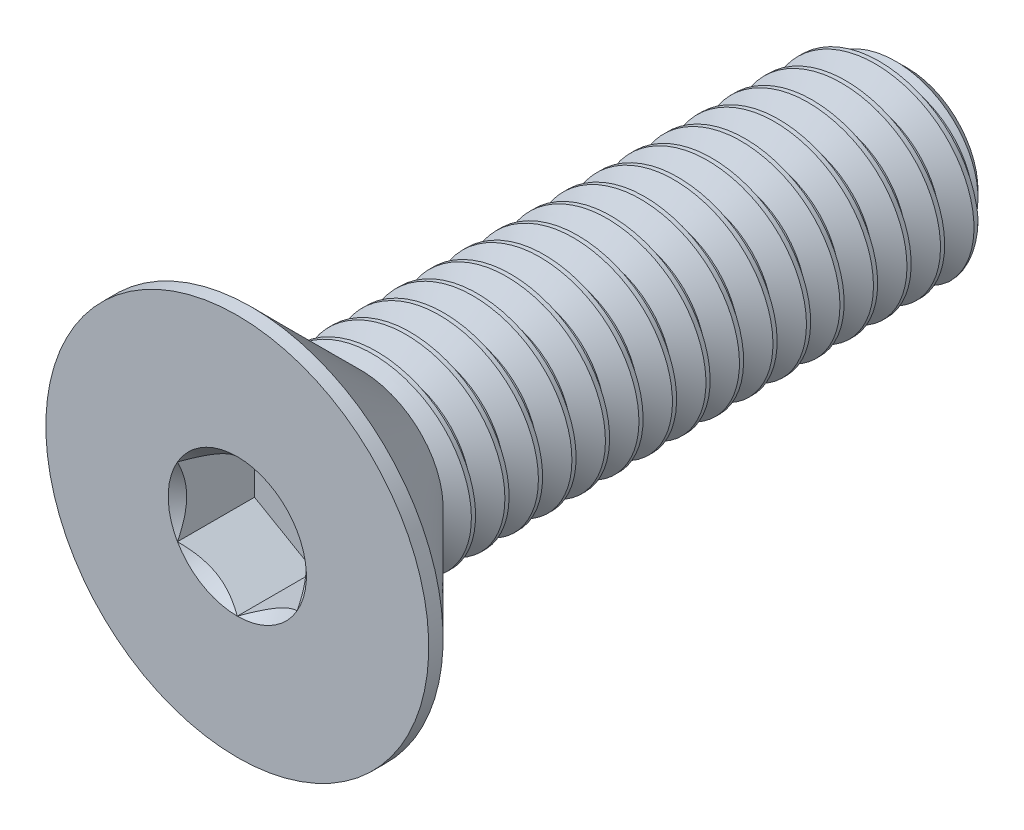
SolidWorks part; units mm, degrees
ref_plane "Front" through (0, 0, 0) normal (0, 0, 1) x (1, 0, 0)
ref_plane "Top" through (0, 0, 0) normal (0, 1, 0) x (1, 0, 0)
ref_plane "Right" through (0, 0, 0) normal (1, 0, 0) x (0, 0, -1)
sketch "Body Sketch" plane through (0, 0, 0) normal (1, 0, 0) x (0, 0, -1)
  line L0 (0, 4) -> (0.3, 4) construction
  line L1 (0.3, 4) -> (2.3, 2) construction
  line L2 (0, 2) -> (14, 2)
  line L3 (14, 2) -> (14, 0)
  line L4 (14, 0) -> (0, 0)
  line L5 (0, 0) -> (0, 4) construction
  line L6 (0, 4) -> (0, -4) construction
  line L7 (14, 2) -> (14, -2) construction
  line L8 (0, -4) -> (0.3, -4) construction
  line L9 (0.3, -4) -> (2.3, -2) construction
  line L11 (0, 2) -> (0, 0)
  line L12 (2.3, 2) -> (2.3, 0) construction
revolve "Body Revolve" add sketch "Body Sketch" angle 360 mid plane about L4
sketch "Sketch3" plane through (0, 0, -14) normal (0, 0, -1) x (-1, 0, 0)
  circle A0 centre (0, 0) radius 2
curve "Helix/Spiral1" pitch 0.7 height 14 radius 2 centre (0, 0, -14) axis (0, 0, 1) start towards (0, 1, 0)
sketch "Sketch2" plane through (0, 0, 0) normal (1, 0, 0) x (0, 0, -1)
  line L0 (14, 2) -> (14.6125, 2)
  line L1 (14.6125, 2) -> (14.35, 1.5453)
  line L2 (14.35, 1.5453) -> (14.2625, 1.5453)
  line L3 (14.2625, 1.5453) -> (14, 2)
  line L4 (14.1312, 1.7727) -> (14.4813, 1.7727) construction
  dimension "D1" = 60
  dimension "D2" = 0.0875
  dimension "D3" = 0.35
chamfer "Chamfer1" distance 0.525 angle 45 1 edges at (0, 2, -14)
sweep "Cut-Sweep1" cut profiles "Sketch2" path "Helix/Spiral1" align with end faces yes
sketch "Head Sketch" plane through (0, 0, 0) normal (1, 0, 0) x (0, 0, -1)
  line L0 (0, 4) -> (0.3, 4) construction
  line L1 (0.3, 4) -> (2.3, 2) construction
  line L2 (0, 4) -> (0.3, 4)
  line L3 (0.3, 4) -> (2.3, 2)
  line L4 (2.3, 2) -> (2.3, 0) construction
  line L5 (2.3, 2) -> (2.3, 0)
  line L7 (0, 0) -> (0, 4) construction
  line L8 (0, 0) -> (0, 4)
  line L9 (0, 0) -> (2.3, 0)
  line L10 (4.4, 0) -> (-4.4, 0) construction
revolve "Head Revolve" add sketch "Head Sketch" angle 360 mid plane about L9
ref_plane "Base of Head Plane" through (0, 0, -2.3) normal (0, 0, 1) x (1, 0, 0)
sketch "Sketch8" plane through (0, 0, -2.3) normal (0, 0, 1) x (1, 0, 0)
  circle A0 centre (0, 0) radius 2
extrude "Boss-Extrude1" add sketch "Sketch8" against normal through all draft 45
sketch "Sketch5" plane through (0, 0, 0) normal (0, 0, 1) x (1, 0, 0)
  line L1 (1.25, -0.7217) -> (1.25, 0.7217)
  line L2 (1.25, 0.7217) -> (0, 1.4434)
  line L3 (0, 1.4434) -> (-1.25, 0.7217)
  line L4 (-1.25, 0.7217) -> (-1.25, -0.7217)
  line L5 (-1.25, -0.7217) -> (0, -1.4434)
  line L6 (0, -1.4434) -> (1.25, -0.7217)
  circle A0 centre (0, 0) radius 1.25 construction
  dimension "Hex" = 2.5
extrude "Cut-Extrude2" cut sketch "Sketch5" against normal blind 1.61
sketch "Sketch6" plane through (0, 0, 0) normal (0, 0, 1) x (1, 0, 0)
  circle A0 centre (0, 0) radius 1.4434
extrude "Cut-Extrude3" cut sketch "Sketch6" against normal blind 1.61 draft 45
equation "\"D3@Helix/Spiral1\" = \"Length@Body Sketch\""
equation "\"D2@Sketch2\" = \"D4@Helix/Spiral1\" * .125"
equation "\"D3@Sketch2\" = \"D4@Helix/Spiral1\" * .5"
equation "\"D1@Chamfer1\" = \"D4@Helix/Spiral1\" * .75"
equation "\"D1@Cut-Extrude2\" = \"Head Ht@Body Sketch\" * .7"
equation "\"D1@Cut-Extrude3\" = \"D1@Cut-Extrude2\""
